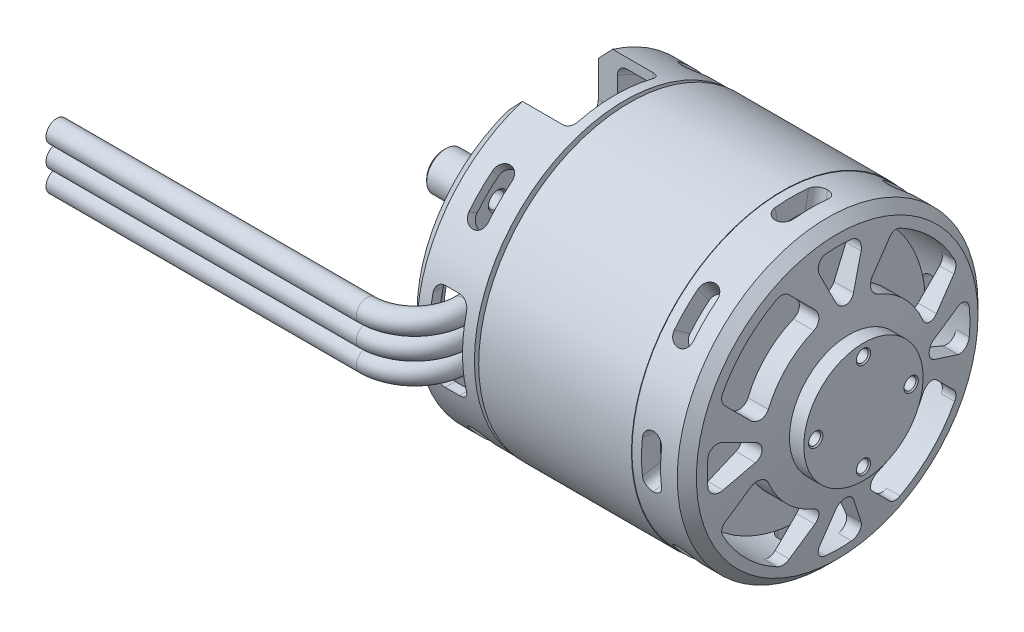
SolidWorks part; units mm, degrees
ref_plane "Front Plane" through (0, 0, 0) normal (0, 0, 1) x (1, 0, 0)
ref_plane "Top Plane" through (0, 0, 0) normal (0, 1, 0) x (1, 0, 0)
ref_plane "Right Plane" through (0, 0, 0) normal (1, 0, 0) x (0, 0, -1)
sketch "Sketch1" plane through (0, 0, 0) normal (0, 1, 0) x (1, 0, 0)
  line L0 (0, 0) -> (0, 4)
  line L1 (0, 4) -> (23, 4)
  line L2 (23, 4) -> (23, 28.5)
  line L3 (23, 28.5) -> (26, 31.5)
  line L4 (26, 31.5) -> (80.5, 31.5)
  line L5 (80.5, 31.5) -> (82.5, 29.5)
  line L6 (82.5, 29.5) -> (85, 12.5)
  line L7 (85, 12.5) -> (85, 0)
  line L8 (85, 0) -> (0, 0) construction
  line L9 (0, 0) -> (85, 0)
  dimension "D1" = 45
  dimension "D2" = 45
  dimension "D3" = 63
  dimension "D4" = 8
  dimension "D5" = 25
  dimension "D6" = 59.5
  dimension "D7" = 3
  dimension "D8" = 62
  dimension "D9" = 85
  dimension "D10" = 62
  dimension "D11" = 2
revolve "Revolve1" add sketch "Sketch1" angle 360 about L8
sketch "Sketch13" plane through (0, 0, 0) normal (0, 1, 0) x (1, 0, 0)
  line L0 (0, 0) -> (107.5015, 0) construction
  line L1 (38, 34.9565) -> (39, 34.9565)
  line L2 (38, 34.9565) -> (38, 4)
  line L3 (38, 4) -> (39, 4)
  line L4 (39, 34.9565) -> (39, 4)
  line L5 (23, 28.5) -> (23, -28.5) construction
  dimension "D1" = 15
  dimension "D2" = 1
  dimension "D3" = 4
revolve "Cut-Revolve1" cut sketch "Sketch13" angle 360 about L0
sketch "Sketch15" plane through (0, 0, 0) normal (0, 1, 0) x (1, 0, 0)
  line L0 (23, -28) -> (26.5, -31.5)
  line L1 (26, 31.5) -> (23, 28.5)
  line L2 (26, 31.5) -> (23, 28.5) construction
  line L3 (27, 13) -> (27, 27.5)
  line L4 (26.5, -31.5) -> (80.5, -31.5)
  line L5 (38, 31.5) -> (26, 31.5)
  line L6 (38, 31.5) -> (26, 31.5) construction
  line L7 (29, 29.5) -> (38, 29.5)
  line L8 (23, 28.5) -> (23, 4)
  line L9 (23, -4) -> (23, -28)
  line L10 (38, 29.5) -> (38, 10)
  line L11 (23, 28.5) -> (23, 4) construction
  line L12 (38, 10) -> (30, 10)
  line L13 (0, 0) -> (100.9095, 0) construction
  line L14 (38, -31.5) -> (38, 31.5) construction
  arc A0 (27, 27.5) -> (29, 29.5) centre (29, 27.5) cw
  arc A1 (27, 13) -> (30, 10) centre (30, 13) ccw
  dimension "D3" = 2
  dimension "D4" = 3
  dimension "D1" = 4
  dimension "D2" = 2
  dimension "D5" = 20
revolve "Cut-Revolve2" cut sketch "Sketch15" angle 360 about L13
sketch "Sketch3" plane through (23, 0, 0) normal (-1, 0, 0) x (0, 0, 1)
  line L0 (-9.45, 30.0491) -> (-9.45, 19.4589)
  line L1 (0, 31.5) -> (0, -31.5) construction
  line L2 (9.45, 30.0491) -> (9.45, 19.4589)
  line L3 (-9.45, -19.4589) -> (-9.45, -30.0491)
  line L4 (9.45, -19.4589) -> (9.45, -30.0491)
  arc A0 (-5.5061, -16.6112) -> (5.5061, -16.6112) centre (0, 0) ccw
  circle A1 centre (0, 0) radius 31.5 construction
  arc A2 (-9.45, -30.0491) -> (9.45, -30.0491) centre (0, 0) ccw
  arc A3 (9.45, 30.0491) -> (-9.45, 30.0491) centre (0, 0) ccw
  arc A4 (5.5061, 16.6112) -> (-5.5061, 16.6112) centre (0, 0) ccw
  arc A5 (5.5061, 16.6112) -> (9.45, 19.4589) centre (6.45, 19.4589) ccw
  arc A6 (-9.45, 19.4589) -> (-5.5061, 16.6112) centre (-6.45, 19.4589) ccw
  arc A7 (-5.5061, -16.6112) -> (-9.45, -19.4589) centre (-6.45, -19.4589) ccw
  arc A8 (5.5061, -16.6112) -> (9.45, -19.4589) centre (6.45, -19.4589) cw
  point P20 (-9.45, -14.7291)
  point P23 (9.45, -14.7291)
  dimension "D2" = 35
  dimension "D3" = 3
  dimension "D1" = 18.9
extrude "Cut-Extrude1" cut sketch "Sketch3" against normal blind 13
sketch "Sketch4" plane through (23, 0, 0) normal (-1, 0, 0) x (0, 0, 1)
  line L0 (0, 0) -> (-42.6061, 0) construction
  line L1 (-42.6061, 10) -> (-19.2678, 10)
  line L2 (-42.6061, 10) -> (-42.6061, -10)
  line L3 (-42.6061, -10) -> (-19.2678, -10)
  arc A0 (-16.4482, 5.9756) -> (-16.4482, -5.9756) centre (0, 0) ccw
  arc A1 (5.5061, 16.6112) -> (-5.5061, 16.6112) centre (0, 0) ccw construction
  arc A2 (-19.2678, -10) -> (-16.4482, -5.9756) centre (-19.2678, -7) ccw
  arc A3 (-19.2678, 10) -> (-16.4482, 5.9756) centre (-19.2678, 7) cw
  arc A4 (-9.45, 19.4589) -> (-5.5061, 16.6112) centre (-6.45, 19.4589) ccw construction
  dimension "D1" = 20
extrude "Cut-Extrude2" cut sketch "Sketch4" against normal up to surface (13 mm away) up to face at (36, -29.7486, 0)
sketch "Sketch5" plane through (23, 0, 0) normal (-1, 0, 0) x (0, 0, 1)
  line L0 (-15.5563, 15.5563) -> (15.5563, -15.5563) construction
  line L1 (15.5563, 15.5563) -> (-15.5563, -15.5563) construction
  line L2 (0, 0) -> (0, 56.0697) construction
  circle A0 centre (0, 0) radius 22 construction
  circle A1 centre (0, 0) radius 15 construction
  point P10 (-10.6066, 10.6066)
  point P11 (10.6066, 10.6066)
  point P12 (10.6066, -10.6066)
  point P14 (-10.6066, -10.6066)
  dimension "D2" = 44
  dimension "D3" = 30
  dimension "D1" = 45
hole_wizard "M4 Tapped Hole1" positions "Sketch6" profile "Sketch7" tap size "M4" standard "DIN" end condition up to next
sketch "Sketch6" plane through (23, 0, 0) normal (-1, 0, 0) x (0, 0, 1)
  point P0 (-15.5563, -15.5563)
  point P3 (-15.5563, 15.5563)
  point P6 (15.5563, 15.5563)
  point P9 (15.5563, -15.5563)
  point P13 (-10.6066, -10.6066)
  point P16 (10.6066, -10.6066)
  point P19 (10.6066, 10.6066)
  point P22 (-10.6066, 10.6066)
cosmetic thread "Hole Thread9" parameters "D2"=4
cosmetic thread "Hole Thread10" parameters "D2"=4
cosmetic thread "Hole Thread11" parameters "D2"=4
cosmetic thread "Hole Thread12" parameters "D2"=4
cosmetic thread "Hole Thread13" parameters "D2"=4
cosmetic thread "Hole Thread14" parameters "D2"=4
cosmetic thread "Hole Thread15" parameters "D2"=4
cosmetic thread "Hole Thread16" parameters "D2"=4
sketch "Sketch7" plane through (23, -15.5563, -15.5563) normal (0, 1, 0) x (0, 0, 1)
  line L0 (0, 0) -> (0, 4)
  line L1 (0, 4) -> (2, 4)
  line L2 (1.65, 3.65) -> (1.65, 0.35)
  line L3 (1.65, 0.35) -> (2, 0)
  line L5 (2, 0) -> (0, 0)
  line L6 (-1.65, 0.35) -> (-2, 0) construction
  line L7 (2, 4) -> (1.65, 3.65)
  line L8 (-2, 4) -> (-1.65, 3.65) construction
  line L11 (0, -6.35) -> (0, 107.95) construction
  dimension "Thru Tap Drill Dia." = 3.3
  dimension "Thru Tap Drill Depth" = 4
  dimension "Near C'Sink Dia." = 4
  dimension "Near C'Sink Angle" = 90
  dimension "Far C'Sink Dia." = 4
  dimension "Far C'Sink Angle" = 90
sketch "Sketch8" plane through (85, 0, 0) normal (1, 0, 0) x (0, 0, -1)
  circle A1 centre (0, 0) radius 12.5
  circle A2 centre (0, 0) radius 12.5
  dimension "D1" = 0
extrude "Boss-Extrude1" add sketch "Sketch8" along normal blind 3
sketch "Sketch9" plane through (23, 0, 0) normal (-1, 0, 0) x (0, 0, 1)
  line L0 (0, 0) -> (27, 0) construction
  line L1 (19.2678, 10) -> (22.9565, 10)
  line L2 (19.2678, -10) -> (22.9565, -10)
  line L3 (-19.2678, 10) -> (-26.688, 10) construction
  arc A0 (16.4482, -5.9756) -> (16.4482, 5.9756) centre (0, 0) ccw
  arc A1 (5.5061, 16.6112) -> (-5.5061, 16.6112) centre (0, 0) ccw construction
  arc A2 (25.826, -7.875) -> (25.826, 7.875) centre (0, 0) ccw
  arc A3 (25.826, 7.875) -> (22.9565, 10) centre (22.9565, 7) ccw
  arc A4 (25.826, -7.875) -> (22.9565, -10) centre (22.9565, -7) cw
  arc A5 (19.2678, -10) -> (16.4482, -5.9756) centre (19.2678, -7) cw
  arc A6 (19.2678, 10) -> (16.4482, 5.9756) centre (19.2678, 7) ccw
  arc A7 (5.5061, 16.6112) -> (9.45, 19.4589) centre (6.45, 19.4589) ccw construction
  point P16 (14.3614, -10)
  point P19 (14.3614, 10)
  dimension "D2" = 27
extrude "Cut-Extrude3" cut sketch "Sketch9" against normal up to surface (13 mm away) up to face at (36, -29.7486, 0)
ref_plane "Plane1" through (0, 0, 50) normal (0, 0, 1) x (1, 0, 0)
sketch "Sketch11" plane through (0, 0, 50) normal (0, 0, 1) x (1, 0, 0)
  line L0 (0, 0) -> (28.5, 0) construction
  line L1 (30.5, 9.25) -> (33.5, 9.25)
  line L2 (28.5, 7.25) -> (28.5, -7.25)
  line L3 (30.5, -9.25) -> (33.5, -9.25)
  line L4 (35.5, 7.25) -> (35.5, -7.25)
  line L5 (23, 15) -> (23, -15) construction
  arc A0 (28.5, -7.25) -> (30.5, -9.25) centre (30.5, -7.25) ccw
  arc A1 (33.5, -9.25) -> (35.5, -7.25) centre (33.5, -7.25) ccw
  arc A2 (30.5, 9.25) -> (28.5, 7.25) centre (30.5, 7.25) ccw
  arc A3 (33.5, 9.25) -> (35.5, 7.25) centre (33.5, 7.25) cw
  dimension "D1" = 2
  dimension "D2" = 5.5
  dimension "D3" = 7
  dimension "D4" = 18.5
extrude "Cut-Extrude4" cut sketch "Sketch11" against normal blind 33
chamfer "Chamfer1" distance 0.5 angle 45 1 edges at (0, 0, -4)
fillet "Fillet1" radius 1.5 6 edges at (36, 28.9973, -9.45) (36, 28.9973, 9.45) (36, -28.9973, -9.45) (36, -28.9973, 9.45) (36, 10, -28.812) (36, -10, -28.812)
ref_plane "Plane3" through (32, 0, 0) normal (-1, 0, 0) x (0, 0, 1)
sketch "Sketch16" plane through (32, 0, 0) normal (-1, 0, 0) x (0, 0, 1)
  line L0 (16.3243, 23.3617) -> (18.0426, 25.8208)
  line L2 (25.8208, 18.0426) -> (23.3617, 16.3243)
  line L3 (15.5563, 15.5563) -> (-15.5563, -15.5563) construction
  line L4 (15.5563, 15.5563) -> (-15.5563, -15.5563) construction
  arc A0 (9.45, -30.0491) -> (9.45, 30.0491) centre (0, 0) ccw construction
  arc A1 (25.8208, 18.0426) -> (18.0426, 25.8208) centre (0, 0) ccw
  arc A2 (9.45, -26.8877) -> (9.45, 26.8877) centre (0, 0) ccw construction
  arc A3 (23.3617, 16.3243) -> (16.3243, 23.3617) centre (0, 0) ccw
  dimension "D1" = 11
extrude "Cut-Extrude5" cut sketch "Sketch16" against normal mid plane 4
fillet "Fillet2" radius 2 4 edges at (34, 17.4698, 25.0011) (30, 17.4698, 25.0011) (30, 25.0011, 17.4698) (34, 25.0011, 17.4698)
pattern_circular "CirPattern1" count 4 over 360 about axis through (85, 0, 0) along (1, 0, 0) of "Cut-Extrude5", "Fillet2"
sketch "Sketch18" plane through (0, 0, 0) normal (0, 1, 0) x (1, 0, 0)
  line L0 (35.5, -31.5) -> (35.5, -29.5)
  line L1 (35.5, -31.5) -> (35.5, -29.5) construction
  line L2 (28.5, -29.4365) -> (28.5, -31.5)
  line L3 (28.5, -29.4365) -> (28.5, -31.5) construction
  line L4 (39, 10) -> (30, 10)
  line L5 (38, -4) -> (39, -4)
  line L6 (38, -4) -> (39, -4) construction
  line L7 (32, -4) -> (32, -28)
  line L8 (22, -38) -> (-43, -38)
  line L9 (28.5, -31.5) -> (35.5, -31.5) construction
  arc A0 (32, -28) -> (22, -38) centre (22, -28) cw
  point P12 (32, -31.5)
  dimension "D1" = 10
  dimension "D2" = 65
  dimension "D3" = 24
ref_plane "Plane5" through (-43, 0, 38) normal (-1, 0, 0) x (0, 0, 1)
sketch "Sketch19" plane through (-43, 0, 38) normal (-1, 0, 0) x (0, 0, 1)
  circle A0 centre (0, 0) radius 2.25
  dimension "D1" = 4.5
sweep "Sweep1" add profiles "Sketch19" path "Sketch18"
move or copy body "Body-Move/Copy1" bodies to move or copy 112 copy yes number of copies 1 translate (0, 4.5, 0)
mirror "Mirror1" about plane through (0, 0, 0) normal (0, 1, 0) of bodies 113
ref_plane "Plane6" through (75, 0, 0) normal (-1, 0, 0) x (0, 0, 1)
sketch "Sketch21" plane through (39, 0, 0) normal (-1, 0, 0) x (0, 0, 1)
  circle A1 centre (0, 0) radius 4 construction
  circle A2 centre (0, 0) radius 27.5
  circle A3 centre (0, 0) radius 27.5
  circle A4 centre (0, 0) radius 4
  dimension "D1" = 4
ref_plane "Plane7" through (80, 0, 0) normal (1, 0, 0) x (0, 0, -1)
extrude "Cut-Extrude7" cut sketch "Sketch21" against normal up to surface (41 mm away) up to plane "Plane7"
sketch "Sketch20" plane through (75, 0, 0) normal (-1, 0, 0) x (0, 0, 1)
  line L0 (23.3617, 16.3243) -> (18.163, 12.6917)
  line L1 (16.3243, 23.3617) -> (12.6917, 18.163)
  line L2 (18.0426, 25.8208) -> (16.3243, 23.3617)
  line L3 (23.3617, 16.3243) -> (25.8208, 18.0426)
  line L4 (18.0426, 25.8208) -> (16.3243, 23.3617)
  line L5 (23.3617, 16.3243) -> (25.8208, 18.0426)
  arc A0 (18.163, 12.6917) -> (12.6917, 18.163) centre (0, 0) ccw
  arc A2 (25.8208, 18.0426) -> (18.0426, 25.8208) centre (0, 0) ccw
  arc A3 (23.3617, 16.3243) -> (16.3243, 23.3617) centre (0, 0) ccw
  arc A4 (25.8208, 18.0426) -> (18.0426, 25.8208) centre (0, 0) ccw
  arc A5 (23.3617, 16.3243) -> (16.3243, 23.3617) centre (0, 0) ccw construction
  dimension "D1" = 0
extrude "Cut-Extrude6" cut sketch "Sketch20" against normal mid plane 4
fillet "Fillet3" radius 2 4 edges at (77, 24.1814, 16.8971) (73, 24.1814, 16.8971) (73, 16.8971, 24.1814) (77, 16.8971, 24.1814)
pattern_circular "CirPattern7" count 8 over 360 about axis through (85, 0, 0) along (1, 0, 0) of "Cut-Extrude6", "Fillet3"
sketch "Sketch22" plane through (75, 0, 0) normal (-1, 0, 0) x (0, 0, 1)
  line L0 (-10.5162, 23.9512) -> (-6.0104, 19.4454)
  line L1 (-34.3401, 34.3401) -> (34.3401, -34.3401) construction
  line L2 (0, 0) -> (0, 52.3089) construction
  line L3 (-23.9512, 10.5162) -> (-19.4454, 6.0104)
  arc A0 (-12.8661, 24.3046) -> (-24.3046, 12.8661) centre (0, 0) ccw
  arc A1 (-6.6631, 16.1819) -> (-16.1819, 6.6631) centre (0, 0) ccw
  circle A2 centre (0, 0) radius 27.5 construction
  arc A3 (-12.8661, 24.3046) -> (-10.5162, 23.9512) centre (-11.9304, 22.537) cw
  arc A4 (-24.3046, 12.8661) -> (-23.9512, 10.5162) centre (-22.537, 11.9304) ccw
  arc A5 (-6.6631, 16.1819) -> (-6.0104, 19.4454) centre (-7.4246, 18.0312) ccw
  arc A6 (-16.1819, 6.6631) -> (-19.4454, 6.0104) centre (-18.0312, 7.4246) cw
  dimension "D3" = 35
  dimension "D4" = 2
  dimension "D1" = 45
  dimension "D2" = 19
extrude "Cut-Extrude8" cut sketch "Sketch22" against normal through all
pattern_circular "CirPattern8" count 4 over 360 about axis through (88, 0, 0) along (1, 0, 0) of "Cut-Extrude8"
sketch "Sketch23" plane through (75, 0, 0) normal (-1, 0, 0) x (0, 0, 1)
  line L0 (4.3404, 24.5943) -> (1.8404, 18.7171)
  line L1 (-1.8404, 18.7171) -> (-4.3404, 24.5943)
  line L2 (0, 0) -> (0, 41.576) construction
  arc A0 (2.6961, 27.3675) -> (-2.6961, 27.3675) centre (0, 0) ccw
  circle A1 centre (0, 0) radius 27.5 construction
  arc A2 (1.8404, 18.7171) -> (-1.8404, 18.7171) centre (0, 19.5) cw
  arc A3 (-4.3404, 24.5943) -> (-2.6961, 27.3675) centre (-2.5, 25.3772) cw
  arc A4 (4.3404, 24.5943) -> (2.6961, 27.3675) centre (2.5, 25.3772) ccw
  arc A5 (-6.6631, 16.1819) -> (-16.1819, 6.6631) centre (0, 0) ccw construction
  dimension "D1" = 2
  dimension "D2" = 5
extrude "Cut-Extrude9" cut sketch "Sketch23" against normal through all
pattern_circular "CirPattern9" count 4 over 360 about axis through (88, 0, 0) along (-1, 0, 0) of "Cut-Extrude9" reverse direction yes
sketch "Sketch24" plane through (88, 0, 0) normal (1, 0, 0) x (0, 0, -1)
  circle A0 centre (0, 0) radius 10 construction
  point P3 (0, 10)
  point P4 (-10, 0)
  point P5 (10, 0)
  point P6 (0, -10)
  dimension "D1" = 20
hole_wizard "M3 Tapped Hole1" positions "Sketch25" profile "Sketch26" tap size "M3" standard "DIN"
sketch "Sketch25" plane through (88, 0, 0) normal (1, 0, 0) x (0, 0, -1)
  point P0 (-10, 0)
  point P3 (0, 10)
  point P6 (10, 0)
  point P9 (0, -10)
sketch "Sketch26" plane through (88, 0, 10) normal (0, 1, 0) x (0, 0, -1)
  line L0 (0, 0) -> (0, 8.2511)
  line L1 (0, 8.2511) -> (1.25, 7.5)
  line L2 (1.25, 7.5) -> (1.25, 0.25)
  line L3 (1.25, 0.25) -> (1.5, 0)
  line L5 (1.5, 0) -> (0, 0)
  line L6 (-1.25, 0.25) -> (-1.5, 0) construction
  line L10 (0, 8.2511) -> (-1.25, 7.5) construction
  line L11 (0, -6.35) -> (0, 107.95) construction
  dimension "Tap Drill Dia." = 2.5
  dimension "Tap Drill Depth" = 7.5
  dimension "Near C'Sink Dia." = 3
  dimension "Near C'Sink Angle" = 90
  dimension "Drill Angle" = 118
cosmetic thread "Hole Thread17" parameters "D1"=6, "D2"=3
cosmetic thread "Hole Thread18" parameters "D1"=6, "D2"=3
cosmetic thread "Hole Thread19" parameters "D1"=6, "D2"=3
cosmetic thread "Hole Thread20" parameters "D1"=6, "D2"=3
ref_axis "Axis1" through (-11.4188, 0, 0) along (1, 0, 0)
sketch "Sketch28" plane through (0, 0, 0) normal (0, 1, 0) x (1, 0, 0)
  line L0 (39, 31.5) -> (39, 31.6)
  line L1 (39, 31.6) -> (71, 31.6)
  line L2 (71, 31.6) -> (71, 31.5)
  line L3 (73, 31.5) -> (39, 31.5) construction
  line L4 (71, 31.5) -> (39, 31.5)
  dimension "D1" = 32
  dimension "D2" = 0.1
revolve "Revolve2" add sketch "Sketch28" angle 360 about axis through (-11.4188, 0, 0) along (1, 0, 0)
sketch "Sketch29" plane through (80, 0, 0) normal (-1, 0, 0) x (0, 0, 1)
  circle A0 centre (0, 0) radius 26
  dimension "D1" = 52
extrude "Boss-Extrude2" add sketch "Sketch29" along normal up to surface (41 mm away) from offset 5 up to face at (39, 0, 27.5)
sketch "Sketch30" plane through (23, 0, 0) normal (-1, 0, 0) x (0, 0, 1)
  circle A0 centre (0, 0) radius 9.5
  circle A1 centre (0, 0) radius 4 construction
  circle A2 centre (0, 0) radius 4
  dimension "D1" = 19
extrude "Boss-Extrude4" add sketch "Sketch30" along normal blind 0.2
